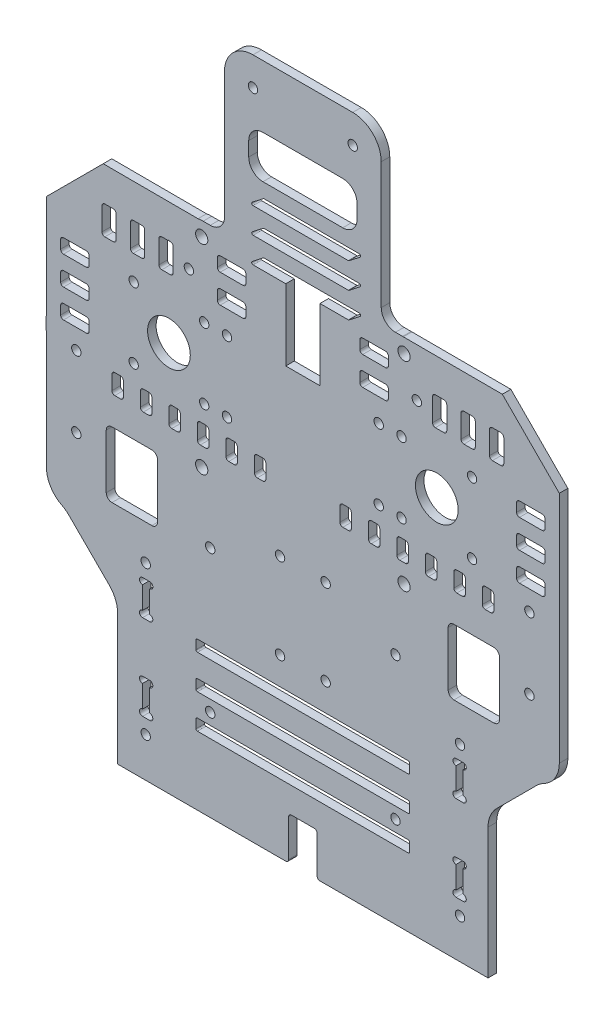
SolidWorks part; units mm, degrees
material "Thornel Mat VMA"
ref_plane "前视基准面" through (0, 0, 0) normal (0, 0, 1) x (1, 0, 0)
ref_plane "上视基准面" through (0, 0, 0) normal (0, 1, 0) x (1, 0, 0)
ref_plane "右视基准面" through (0, 0, 0) normal (1, 0, 0) x (0, 0, -1)
sketch "草图1" plane through (0, 0, 0) normal (0, 0, 1) x (1, 0, 0)
  line L1 (105, -75) -> (-105, -75)
  line L2 (105, -75) -> (105, 75)
  line L3 (105, 75) -> (-105, 75)
  line L4 (-105, -75) -> (-105, 75)
  line L5 (105, -75) -> (-105, 75) construction
  line L6 (105, 75) -> (-105, -75) construction
  line L7 (35.5, -25) -> (-35.5, -25) construction
  line L8 (35.5, -25) -> (35.5, 45) construction
  line L9 (35.5, 45) -> (-35.5, 45) construction
  line L10 (-35.5, -25) -> (-35.5, 45) construction
  line L11 (35.5, -25) -> (-35.5, 45) construction
  line L12 (35.5, 45) -> (-35.5, -25) construction
  circle A0 centre (-35.5, 45) radius 2.15
  circle A1 centre (35.5, 45) radius 2.15
  circle A2 centre (-35.5, -25) radius 2.15
  circle A3 centre (35.5, -25) radius 2.15
  point P0 (0, 0)
  point P5 (0, 10)
  dimension "D6" = 4.3
  dimension "D7" = 4.3
  dimension "D8" = 4.3
  dimension "D9" = 4.3
  dimension "D1" = 150
  dimension "D2" = 210
  dimension "D3" = 70
  dimension "D4" = 71
  dimension "D5" = 10
extrude "凸台-拉伸1" add sketch "草图1" along normal blind 3
sketch "草图2" plane through (0, 0, 3) normal (0, 0, 1) x (1, 0, 0)
  line L0 (0, 0) -> (0, -58.5464) construction
  circle A0 centre (-8, -38.3) radius 1.65
  circle A1 centre (-8, -68.3) radius 1.65
  circle A2 centre (-35.5, -25) radius 2.15 construction
  circle A3 centre (8, -68.3) radius 1.65
  circle A4 centre (8, -38.3) radius 1.65
  dimension "D1" = 3.3
  dimension "D2" = 3.3
  dimension "D4" = 27.5
  dimension "D5" = 13.3
  dimension "D3" = 30
extrude "切除-拉伸1" cut sketch "草图2" against normal blind 10
sketch "草图3" plane through (0, 0, 0) normal (0, 0, -1) x (-1, 0, 0)
  line L0 (34.6256, -5.3744) -> (34.6256, 19.3744) construction
  line L1 (-28.75, 7) -> (98.7077, 7) construction
  line L2 (0, 0) -> (0, 47.7438) construction
  line L3 (-34.6256, -5.3744) -> (-59.3744, -5.3744) construction
  line L7 (-34.6256, -5.3744) -> (-34.6256, 19.3744) construction
  line L8 (-34.6256, 19.3744) -> (-59.3744, 19.3744) construction
  line L9 (-59.3744, -5.3744) -> (-59.3744, 19.3744) construction
  line L10 (-34.6256, -5.3744) -> (-59.3744, 19.3744) construction
  line L11 (-34.6256, 19.3744) -> (-59.3744, -5.3744) construction
  line L12 (59.3744, -5.3744) -> (59.3744, 19.3744) construction
  circle A0 centre (-47, 7) radius 7.5
  circle A1 centre (47, 7) radius 7.5
  circle A2 centre (-59.3744, 19.3744) radius 1.65
  circle A9 centre (-34.6256, 19.3744) radius 1.65
  circle A10 centre (-59.3744, -5.3744) radius 1.65
  circle A11 centre (-34.6256, -5.3744) radius 1.65
  circle A12 centre (34.6256, -5.3744) radius 1.65
  circle A13 centre (34.6256, 19.3744) radius 1.65
  circle A14 centre (59.3744, -5.3744) radius 1.65
  circle A15 centre (59.3744, 19.3744) radius 1.65
  dimension "D1" = 15
  dimension "D2" = 94
  dimension "D3" = 17.5
  dimension "D4" = 3.3
  dimension "D7" = 7
extrude "切除-拉伸2" cut sketch "草图3" against normal blind 10
sketch "草图4" plane through (0, 75, 0) normal (0, 1, 0) x (1, 0, 0)
  line L0 (105, 0) -> (-105, 0) construction
  line L1 (27.5, -3) -> (-27.5, -3)
  line L2 (27.5, -3) -> (27.5, 0)
  line L3 (27.5, 0) -> (-27.5, 0)
  line L4 (-27.5, -3) -> (-27.5, 0)
  line L5 (27.5, -3) -> (-27.5, 0) construction
  line L6 (27.5, 0) -> (-27.5, -3) construction
  point P0 (0, -1.5)
  dimension "D1" = 3
  dimension "D2" = 55
extrude "凸台-拉伸2" add sketch "草图4" along normal blind 34.32
fillet "圆角1" radius 10 2 edges at (27.5, 109.32, 1.5) (-27.5, 109.32, 1.5)
sketch "草图5" plane through (0, 0, 3) normal (0, 0, 1) x (1, 0, 0)
  circle A0 centre (-17.5, 99.32) radius 1.65
  circle A1 centre (17.5, 99.32) radius 1.65
  dimension "D1" = 3.3
  dimension "D2" = 3.3
extrude "切除-拉伸3" cut sketch "草图5" against normal blind 50
sketch "草图6" plane through (0, -75, 0) normal (0, -1, 0) x (1, 0, 0)
  line L4 (-105, 0) -> (105, 0)
  line L5 (105, 0) -> (105, 3)
  line L6 (105, 3) -> (-105, 3)
  line L7 (-105, 3) -> (-105, 0)
  line L8 (-105, 0) -> (105, 0)
  line L9 (105, 0) -> (105, 3)
  line L10 (105, 3) -> (-105, 3)
  line L11 (-105, 3) -> (-105, 0)
  dimension "D1" = 0
extrude "凸台-拉伸3" add sketch "草图6" along normal blind 50
sketch "草图7" plane through (0, 0, 3) normal (0, 0, 1) x (1, 0, 0)
  line L1 (-27.5, 75) -> (-105, 75)
  line L2 (-27.5, 75) -> (-27.5, 50)
  line L3 (-27.5, 50) -> (-105, 50)
  line L4 (-105, 75) -> (-105, 50)
  line L5 (-105, 75) -> (-105, -125) construction
  line L7 (27.5, 75) -> (105, 75)
  line L8 (27.5, 75) -> (27.5, 50)
  line L9 (27.5, 50) -> (105, 50)
  line L10 (105, 75) -> (105, 50)
  line L11 (105, -125) -> (105, 75) construction
  dimension "D1" = 25
  dimension "D2" = 77.5
  dimension "D3" = 25
  dimension "D4" = 77.5
extrude "切除-拉伸4" cut sketch "草图7" against normal blind 50
fillet "圆角2" radius 5 2 edges at (27.5, 50, 1.5) (-27.5, 50, 1.5)
chamfer "倒角1" distance 40 distance2 20 2 edges at (105, 50, 1.5) (-105, 50, 1.5) first distance on face at (68.75, 50, 1.5) first distance on face at (-68.75, 50, 1.5)
sketch "草图10" plane through (0, 0, 3) normal (0, 0, 1) x (1, 0, 0)
  line L0 (105, -125) -> (-105, -125) construction
  line L1 (19, -13.5) -> (-19, -13.5)
  line L2 (19, -13.5) -> (19, 28.5)
  line L3 (19, 28.5) -> (10, 28.5)
  line L4 (-19, -13.5) -> (-19, 28.5)
  line L5 (19, -13.5) -> (-19, 28.5) construction
  line L6 (19, 28.5) -> (0, 7.5) construction
  line L7 (-10, 28.5) -> (-10, 60)
  line L9 (10, 28.5) -> (10, 60)
  line L10 (10, 60) -> (-10, 60)
  line L12 (10, 0) -> (-10, 60) construction
  line L13 (10, 60) -> (-10, 0) construction
  line L14 (-10, 28.5) -> (-19, 28.5)
  point P0 (0, 7.5)
  point P12 (0, 30)
  dimension "D1" = 42
  dimension "D2" = 38
  dimension "D3" = 111.5
  dimension "D4" = 60
  dimension "D5" = 20
extrude "切除-拉伸7" cut sketch "草图10" against normal blind 13
fillet "圆角3" radius 2 8 edges at (19, -13.5, 1.5) (-19, -13.5, 1.5) (-19, 28.5, 1.5) (-10, 28.5, 1.5) (10, 28.5, 1.5) (19, 28.5, 1.5) (10, 60, 1.5) (-10, 60, 1.5)
sketch "草图11" plane through (0, 0, 3) normal (0, 0, 1) x (1, 0, 0)
  line L0 (0, 0) -> (0, 66.5643) construction
  circle A0 centre (-14.35, 31.62) radius 2.1
  circle A1 centre (-47, 7) radius 7.5 construction
  circle A2 centre (14.35, 31.62) radius 2.1
  dimension "D1" = 4.2
  dimension "D2" = 28.7
  dimension "D3" = 24.62
extrude "切除-拉伸8" cut sketch "草图11" against normal blind 10
sketch "草图12" plane through (0, 0, 3) normal (0, 0, 1) x (1, 0, 0)
  line L0 (-14.35, 31.62) -> (14.35, 31.62) construction
  line L1 (0, 31.62) -> (0, -16.21) construction
  circle A0 centre (0, -16.21) radius 2.2
  dimension "D1" = 4.4
  dimension "D2" = 47.83
extrude "切除-拉伸9" cut sketch "草图12" against normal blind 10
sketch "草图19" plane through (0, -125, 0) normal (0, -1, 0) x (1, 0, 0)
  line L4 (-105, 3) -> (-105, 0)
  line L5 (-105, 0) -> (105, 0)
  line L6 (-105, 3) -> (-105, 0)
  line L7 (105, 3) -> (-105, 3)
  line L9 (-105, 0) -> (105, 0)
  line L11 (105, 3) -> (-105, 3)
  line L12 (105, 0) -> (105, 3)
  line L13 (105, 0) -> (105, 3)
  dimension "D1" = 0
extrude "凸台-拉伸4" add sketch "草图19" along normal blind 10
sketch "草图14" plane through (0, 0, 3) normal (0, 0, 1) x (1, 0, 0)
  line L0 (-105, 30) -> (-105, -135) construction
  line L1 (-105, -140.9011) -> (-90, -140.9011)
  line L2 (-105, -140.9011) -> (-105, 59.0989)
  line L3 (-105, 59.0989) -> (-90, 59.0989)
  line L4 (-90, -140.9011) -> (-90, 59.0989)
  line L5 (90, -129.2813) -> (105, -129.2813)
  line L6 (90, -129.2813) -> (90, 70.7187)
  line L7 (90, 70.7187) -> (105, 70.7187)
  line L8 (105, -129.2813) -> (105, 70.7187)
  line L9 (105, -135) -> (105, 30) construction
  dimension "D1" = 200
  dimension "D2" = 15
extrude "切除-拉伸11" cut sketch "草图14" against normal blind 10
sketch "草图17" plane through (0, 0, 3) normal (0, 0, 1) x (1, 0, 0)
  circle A2 centre (-40, 33) radius 1.65
  circle A3 centre (40, 33) radius 1.65
  dimension "D1" = 80
  dimension "D2" = 40
  dimension "D3" = 33
  dimension "D4" = 3.3
  dimension "D5" = 3.3
extrude "切除-拉伸14" cut sketch "草图17" against normal blind 10
sketch "草图20" plane through (0, 0, 3) normal (0, 0, 1) x (1, 0, 0)
  line L1 (90, -129.2813) -> (116.0619, -129.2813)
  line L2 (90, -129.2813) -> (90, -144.7625)
  line L3 (90, -144.7625) -> (116.0619, -144.7625)
  line L4 (116.0619, -129.2813) -> (116.0619, -144.7625)
extrude "切除-拉伸16" cut sketch "草图20" against normal blind 10
fillet "圆角6" radius 5 6 edges at (90, 37.5, 1.5) (65, 50, 1.5) (-65, 50, 1.5) (-90, 37.5, 1.5) (90, -135, 1.5) (-90, -135, 1.5)
sketch "草图21" plane through (0, 0, 3) normal (0, 0, 1) x (1, 0, 0)
  line L0 (-47, 38) -> (-47, 50)
  line L1 (-63.8197, 50) -> (-32.5, 50) construction
  line L2 (-47, 50) -> (-106.4836, 50)
  line L3 (-106.4836, 50) -> (-107.7614, 0)
  line L4 (-107.7614, 0) -> (-77.1993, 0)
  line L5 (78, 7) -> (106.4751, 7)
  line L6 (106.4751, 7) -> (106.4751, 75.5735)
  line L7 (106.4751, 75.5735) -> (47, 75.5735)
  line L8 (47, 75.5735) -> (47, 38)
  arc A0 (-47, 38) -> (-77.1993, 0) centre (-47, 7) ccw
  arc A1 (78, 7) -> (47, 38) centre (47, 7) ccw
  dimension "D1" = 62
  dimension "D2" = 62
extrude "切除-拉伸19" cut sketch "草图21" against normal blind 10
fillet "圆角7" radius 12 4 edges at (90, 7, 1.5) (47, 50, 1.5) (-90, 0, 1.5) (-47, 50, 1.5)
fillet "圆角8" radius 12 2 edges at (78, 7, 1.5) (47, 38, 1.5)
sketch "草图22" plane through (0, 0, 3) normal (0, 0, 1) x (1, 0, 0)
  line L4 (0, 0) -> (0, 90.8471) construction
  line L5 (-90, -12) -> (-70.9724, 1.1695)
  line L6 (-70.9724, 1.1695) -> (-64.1055, 22.5626)
  line L7 (-64.1055, 22.5626) -> (-46.1458, 39.0697)
  line L8 (-46.1458, 39.0697) -> (-35, 50)
  arc A2 (-35, 50) -> (-90, -12) centre (-31.5, -8.5) ccw
  arc A22 (45.6725, 43.4861) -> (35, 50) centre (35, 38) ccw construction
  arc A23 (45.6725, 43.4861) -> (53.7371, 37.2591) centre (56.345, 48.9723) ccw construction
  arc A24 (77.2591, 13.7371) -> (53.7371, 37.2591) centre (47, 7) ccw construction
  arc A25 (77.2591, 13.7371) -> (83.4861, 5.6725) centre (88.9723, 16.345) ccw construction
  arc A26 (90, -5) -> (83.4861, 5.6725) centre (78, -5) ccw construction
  arc A31 (45.6725, 43.4861) -> (35, 50) centre (35, 38) ccw
  arc A32 (45.6725, 43.4861) -> (53.7371, 37.2591) centre (56.345, 48.9723) ccw
  arc A33 (77.2591, 13.7371) -> (53.7371, 37.2591) centre (47, 7) ccw
  arc A34 (77.2591, 13.7371) -> (83.4861, 5.6725) centre (88.9723, 16.345) ccw
  arc A35 (90, -5) -> (83.4861, 5.6725) centre (78, -5) ccw
  arc A36 (35, 50) -> (90, -5) centre (35, -5) cw
extrude "凸台-拉伸5" add sketch "草图22" against normal up to surface (3 mm away) up to face at (-38.35, 33, 0)
sketch "草图24" plane through (0, 0, 3) normal (0, 0, 1) x (1, 0, 0)
  line L1 (-90, -135) -> (-45, -135)
  line L2 (-90, -135) -> (-90, -50)
  line L3 (-90, -50) -> (-45, -50)
  line L4 (-45, -135) -> (-45, -50)
  line L5 (90, -135) -> (45, -135)
  line L6 (90, -135) -> (90, -50)
  line L7 (90, -50) -> (45, -50)
  line L8 (45, -135) -> (45, -50)
  line L9 (85, -135) -> (-85, -135) construction
  dimension "D1" = 85
  dimension "D2" = 45
  dimension "D3" = 85
  dimension "D4" = 45
extrude "切除-拉伸20" cut sketch "草图24" against normal blind 10
sketch "草图25" plane through (0, 0, 3) normal (0, 0, 1) x (1, 0, 0)
  line L1 (-45, -135) -> (45, -135)
  line L2 (-45, -135) -> (-45, -130)
  line L3 (-45, -130) -> (45, -130)
  line L4 (45, -135) -> (45, -130)
  line L5 (45, -50) -> (45, -135) construction
  dimension "D1" = 5
  dimension "D2" = 90
extrude "切除-拉伸21" cut sketch "草图25" against normal blind 30
sketch "草图26" plane through (0, 0, 3) normal (0, 0, 1) x (1, 0, 0)
  line L1 (32.5, -98) -> (-32.5, -98) construction
  line L2 (32.5, -98) -> (32.5, -48) construction
  line L3 (32.5, -48) -> (-32.5, -48) construction
  line L4 (-32.5, -98) -> (-32.5, -48) construction
  line L5 (32.5, -98) -> (-32.5, -48) construction
  line L6 (32.5, -48) -> (-32.5, -98) construction
  circle A0 centre (-32.5, -48) radius 1.65
  circle A1 centre (32.5, -48) radius 1.65
  circle A2 centre (-32.5, -98) radius 1.65
  circle A3 centre (32.5, -98) radius 1.65
  point P0 (0, -73)
  dimension "D1" = 3.3
  dimension "D2" = 3.3
  dimension "D3" = 3.3
  dimension "D4" = 3.3
  dimension "D5" = 65
  dimension "D6" = 73
  dimension "D7" = 50
extrude "切除-拉伸22" cut sketch "草图26" against normal blind 10
sketch "草图27" plane through (0, 0, 3) normal (0, 0, 1) x (1, 0, 0)
  line L0 (-45, -130) -> (-45, -50) construction
  line L1 (0, 0) -> (0, -119.9082) construction
  circle A0 centre (-40, -93) radius 1.65
  circle A1 centre (-35.5, -25) radius 2.15 construction
  circle A2 centre (40, -93) radius 1.65
  circle A3 centre (-40, -125) radius 1.65
  circle A4 centre (40, -125) radius 1.65
  dimension "D1" = 3.3
  dimension "D2" = 5
  dimension "D3" = 68
  dimension "D4" = 3.3
  dimension "D5" = 3.3
  dimension "D6" = 32
extrude "切除-拉伸23" cut sketch "草图27" against normal blind 10
sketch "草图28" plane through (0, 0, 3) normal (0, 0, 1) x (1, 0, 0)
  line L10 (-90, -12) -> (-90, 50)
  line L11 (-90, 50) -> (-36.7963, 49.8648)
  line L12 (90, -5) -> (90, 49.8648)
  line L13 (90, 49.8648) -> (35, 50)
  arc A8 (-36.7963, 49.8648) -> (-90, -12) centre (13.2997, -47.0278) ccw
  arc A9 (90, -5) -> (35, 50) centre (5.4098, -34.5902) ccw
extrude "凸台-拉伸6" add sketch "草图28" against normal up to surface (3 mm away) up to face at (41.65, -93, 0)
sketch "草图29" plane through (0, 0, 3) normal (0, 0, 1) x (1, 0, 0)
  line L1 (19, 72.5) -> (-19, 72.5)
  line L2 (19, 72.5) -> (19, 87.5)
  line L3 (19, 87.5) -> (-19, 87.5)
  line L4 (-19, 72.5) -> (-19, 87.5)
  line L5 (19, 72.5) -> (-19, 87.5) construction
  line L6 (19, 87.5) -> (-19, 72.5) construction
  point P0 (0, 80)
  dimension "D1" = 80
  dimension "D2" = 38
  dimension "D3" = 15
extrude "切除-拉伸24" cut sketch "草图29" against normal blind 5
fillet "圆角10" radius 5 4 edges at (19, 72.5, 1.5) (-19, 72.5, 1.5) (19, 87.5, 1.5) (-19, 87.5, 1.5)
sketch "草图31" plane through (0, 0, 3) normal (0, 0, 1) x (1, 0, 0)
  line L0 (-45, -114) -> (45, -114) construction
  line L1 (45, -50) -> (45, -130) construction
  line L2 (-45, -130) -> (-45, -50) construction
  line L3 (45, -130) -> (-45, -130) construction
  text T0 "<b>WH</b>" font "Mistral" height 17
  dimension "D1" = 16
sketch "草图32" plane through (0, 0, 3) normal (0, 0, 1) x (1, 0, 0)
  line L0 (-40, -93) -> (40, -93) construction
  text T0 "HIT" font "Mistral" height 17
sketch "草图35" plane through (0, 0, 3) normal (0, 0, 1) x (1, 0, 0)
  circle A0 centre (-40, -93) radius 1.8443
  circle A1 centre (-40, -125) radius 3.6058
  circle A2 centre (40, -125) radius 3.1105
  circle A3 centre (40, -93) radius 3.0337
extrude "凸台-拉伸7" add sketch "草图35" against normal up to surface (3 mm away) up to face at (0, 80, 0)
sketch "草图36" plane through (0, 0, 3) normal (0, 0, 1) x (1, 0, 0)
  line L1 (-45, -50) -> (-65, -50)
  line L2 (-45, -50) -> (-45, -130)
  line L3 (-45, -130) -> (-65, -130)
  line L4 (-65, -50) -> (-65, -130)
  line L5 (45, -50) -> (65, -50)
  line L6 (45, -50) -> (45, -130)
  line L7 (45, -130) -> (65, -130)
  line L8 (65, -50) -> (65, -130)
  dimension "D1" = 80
  dimension "D2" = 20
  dimension "D3" = 80
  dimension "D4" = 20
extrude "凸台-拉伸8" add sketch "草图36" against normal up to surface (3 mm away) up to face at (0, 80, 0)
sketch "草图37" plane through (0, 0, 0) normal (0, 0, -1) x (-1, 0, 0)
  line L0 (65, -90) -> (-65, -90) construction
  line L1 (53.75, -81.1) -> (56.25, -81.1)
  line L2 (53.75, -78.9) -> (53.75, -71.1)
  line L3 (53.75, -68.9) -> (56.25, -68.9)
  line L4 (56.25, -78.9) -> (56.25, -71.1)
  line L5 (53.75, -81.1) -> (56.25, -68.9) construction
  line L6 (53.75, -68.9) -> (56.25, -81.1) construction
  line L7 (65, -50) -> (65, -130) construction
  line L8 (-65, -130) -> (-65, -50) construction
  line L9 (53.75, -111.1) -> (56.25, -111.1)
  line L10 (56.25, -101.1) -> (56.25, -108.9)
  line L11 (53.75, -98.9) -> (56.25, -98.9)
  line L12 (53.75, -101.1) -> (53.75, -108.9)
  line L13 (0, 0) -> (0, -157.7378) construction
  line L14 (-53.75, -98.9) -> (-56.25, -98.9)
  line L15 (-53.75, -101.1) -> (-53.75, -108.9)
  line L16 (-53.75, -111.1) -> (-56.25, -111.1)
  line L17 (-56.25, -101.1) -> (-56.25, -108.9)
  line L18 (-53.75, -81.1) -> (-56.25, -81.1)
  line L19 (-53.75, -78.9) -> (-53.75, -71.1)
  line L20 (-53.75, -68.9) -> (-56.25, -68.9)
  line L21 (-56.25, -78.9) -> (-56.25, -71.1)
  arc A0 (56.25, -71.1) -> (56.25, -68.9) centre (56.25, -70) ccw
  arc A1 (53.75, -68.9) -> (53.75, -71.1) centre (53.75, -70) ccw
  arc A2 (56.25, -81.1) -> (56.25, -78.9) centre (56.25, -80) ccw
  arc A3 (53.75, -78.9) -> (53.75, -81.1) centre (53.75, -80) ccw
  arc A4 (56.25, -101.1) -> (56.25, -98.9) centre (56.25, -100) ccw
  arc A5 (53.75, -98.9) -> (53.75, -101.1) centre (53.75, -100) ccw
  arc A6 (56.25, -111.1) -> (56.25, -108.9) centre (56.25, -110) ccw
  arc A7 (53.75, -108.9) -> (53.75, -111.1) centre (53.75, -110) ccw
  arc A8 (-56.25, -101.1) -> (-56.25, -98.9) centre (-56.25, -100) cw
  arc A9 (-53.75, -98.9) -> (-53.75, -101.1) centre (-53.75, -100) cw
  arc A10 (-53.75, -108.9) -> (-53.75, -111.1) centre (-53.75, -110) cw
  arc A11 (-56.25, -111.1) -> (-56.25, -108.9) centre (-56.25, -110) cw
  arc A12 (-56.25, -81.1) -> (-56.25, -78.9) centre (-56.25, -80) cw
  arc A13 (-53.75, -78.9) -> (-53.75, -81.1) centre (-53.75, -80) cw
  arc A14 (-53.75, -68.9) -> (-53.75, -71.1) centre (-53.75, -70) cw
  arc A15 (-56.25, -71.1) -> (-56.25, -68.9) centre (-56.25, -70) cw
  point P0 (55, -75)
  dimension "D5" = 2.2
  dimension "D6" = 2.2
  dimension "D7" = 2.2
  dimension "D8" = 2.2
  dimension "D9" = 2.2
  dimension "D10" = 2.2
  dimension "D11" = 2.2
  dimension "D12" = 2.2
  dimension "D1" = 12.2
  dimension "D2" = 2.5
  dimension "D3" = 55
  dimension "D4" = 75
extrude "切除-拉伸30" cut sketch "草图37" against normal through all
sketch "草图38" plane through (0, 0, 3) normal (0, 0, 1) x (1, 0, 0)
  line L0 (-56.25, -78.9) -> (-56.25, -71.1) construction
  line L1 (-56.25, -68.9) -> (-53.75, -68.9) construction
  line L2 (-56.25, -108.9) -> (-56.25, -101.1) construction
  line L3 (-53.75, -111.1) -> (-56.25, -111.1) construction
  line L4 (0, 0) -> (0, -138.952) construction
  circle A0 centre (-55.15, -63.9) radius 1.65
  circle A1 centre (-55.15, -116.1) radius 1.65
  circle A2 centre (55.15, -116.1) radius 1.65
  circle A3 centre (55.15, -63.9) radius 1.65
  dimension "D1" = 3.3
  dimension "D2" = 1.1
  dimension "D4" = 3.3
  dimension "D6" = 5
  dimension "D3" = 5
  dimension "D5" = 1.1
extrude "切除-拉伸31" cut sketch "草图38" against normal blind 12
sketch "草图39" plane through (0, 0, 3) normal (0, 0, 1) x (1, 0, 0)
  line L0 (8, 60) -> (-8, 60) construction
  line L1 (19, -24.4313) -> (-19, -24.4313)
  line L2 (19, -24.4313) -> (19, 60)
  line L3 (19, 60) -> (-19, 60)
  line L4 (-19, -24.4313) -> (-19, 60)
  line L5 (19, -24.4313) -> (-19, 60) construction
  line L6 (19, 60) -> (-19, -24.4313) construction
  line L7 (19, -11.5) -> (19, 26.5) construction
  line L8 (-19, 26.5) -> (-19, -11.5) construction
  point P0 (0, 17.7844)
extrude "凸台-拉伸9" add sketch "草图39" against normal up to surface (3 mm away) up to face at (56.8, -63.9, 0)
sketch "草图40" plane through (0, 0, 3) normal (0, 0, 1) x (1, 0, 0)
  line L0 (-13.7722, 67.5) -> (-18.9064, 63.5)
  line L1 (-13.7722, 67.5) -> (21.2278, 67.5)
  line L2 (-18.9064, 63.5) -> (16.0936, 63.5)
  line L3 (21.2278, 67.5) -> (16.0936, 63.5)
  line L4 (-13.7722, 58.5) -> (-18.9064, 54.5)
  line L5 (-13.7722, 58.5) -> (21.2278, 58.5)
  line L6 (-18.9064, 54.5) -> (16.0936, 54.5)
  line L7 (21.2278, 58.5) -> (16.0936, 54.5)
  line L8 (-13.7722, 49.5) -> (-18.9064, 45.5)
  line L9 (-13.7722, 49.5) -> (21.2278, 49.5)
  line L10 (-18.9064, 45.5) -> (16.0936, 45.5)
  line L11 (21.2278, 49.5) -> (16.0936, 45.5)
  line L12 (-14, 72.5) -> (14, 72.5) construction
  dimension "D1" = 5
  dimension "D2" = 5
  dimension "D3" = 5
  dimension "D4" = 4
  dimension "D5" = 35
  dimension "D6" = 4
  dimension "D7" = 4
  dimension "D8" = 35
  dimension "D9" = 35
extrude "切除-拉伸32" cut sketch "草图40" against normal blind 10
fillet "圆角13" radius 0.5 12 edges at (21.2278, 49.5, 1.5) (21.2278, 58.5, 1.5) (-13.7722, 49.5, 1.5) (-13.7722, 58.5, 1.5) (-18.9064, 45.5, 1.5) (-18.9064, 54.5, 1.5) (16.0936, 45.5, 1.5) (16.0936, 54.5, 1.5) (16.0936, 63.5, 1.5) (21.2278, 67.5, 1.5) (-18.9064, 63.5, 1.5) (-13.7722, 67.5, 1.5)
sketch "草图42" plane through (0, 0, 3) normal (0, 0, 1) x (1, 0, 0)
  line L0 (0, 0) -> (0, 28.5736) construction
  circle A1 centre (-26.6256, 19.3744) radius 1.65
  circle A2 centre (-26.6256, -5.3744) radius 1.65
  circle A3 centre (-34.6256, 19.3744) radius 1.65 construction
  circle A4 centre (-34.6256, -5.3744) radius 1.65 construction
  circle A5 centre (26.6256, -5.3744) radius 1.65
  circle A6 centre (26.6256, 19.3744) radius 1.65
  dimension "D1" = 3.3
  dimension "D2" = 3.3
  dimension "D3" = 8
  dimension "D4" = 8
extrude "切除-拉伸34" cut sketch "草图42" against normal blind 3
sketch "草图43" plane through (0, 0, 3) normal (0, 0, 1) x (1, 0, 0)
  line L0 (65, -130) -> (-65, -130) construction
  line L1 (5, -145) -> (-5, -145)
  line L2 (5, -145) -> (5, -115)
  line L3 (5, -115) -> (-5, -115)
  line L4 (-5, -145) -> (-5, -115)
  line L5 (5, -145) -> (-5, -115) construction
  line L6 (5, -115) -> (-5, -145) construction
  point P0 (0, -130)
  dimension "D1" = 30
  dimension "D2" = 10
extrude "切除-拉伸35" cut sketch "草图43" against normal blind 10
fillet "圆角15" radius 1 4 edges at (-5, -130, 1.5) (5, -130, 1.5) (5, -115, 1.5) (-5, -115, 1.5)
sketch "草图44" plane through (0, -50, 0) normal (0, -1, 0) x (1, 0, 0)
  line L4 (-90, 0) -> (-65, 0)
  line L5 (-65, 0) -> (-65, 3)
  line L6 (-65, 3) -> (-90, 3)
  line L7 (-90, 3) -> (-90, 0)
  line L8 (-90, 0) -> (-65, 0)
  line L9 (-65, 0) -> (-65, 3)
  line L10 (-65, 3) -> (-90, 3)
  line L11 (-90, 3) -> (-90, 0)
  line L12 (90, 3) -> (65, 3)
  line L13 (65, 3) -> (65, 0)
  line L14 (65, 0) -> (90, 0)
  line L15 (90, 0) -> (90, 3)
  line L16 (90, 3) -> (65, 3)
  line L17 (65, 3) -> (65, 0)
  line L18 (65, 0) -> (90, 0)
  line L19 (90, 0) -> (90, 3)
  dimension "D1" = 0
  dimension "D2" = 0
extrude "凸台-拉伸10" add sketch "草图44" along normal blind 10
sketch "草图9" plane through (0, 0, 3) normal (0, 0, 1) x (1, 0, 0)
  line L0 (-69.75, -24) -> (-105, -24) construction
  line L2 (-79.5, -36.5) -> (-79.5, -11.5) construction
  line L3 (0, 0) -> (0, 51.3549) construction
  line L4 (79.5, -36.5) -> (79.5, -11.5) construction
  line L5 (-35, 50) -> (-32.5, 50) construction
  arc A0 (-90, -5) -> (-90, -12) centre (-31.5, -8.5) ccw construction
  circle A1 centre (-79.5, -11.5) radius 1.65
  circle A2 centre (-79.5, -36.5) radius 1.65
  circle A3 centre (79.5, -36.5) radius 1.65
  circle A4 centre (79.5, -11.5) radius 1.65
  point P9 (-79.5, -24)
  point P18 (79.5, -24)
  point P20 (-90.1046, -8.5)
  dimension "D3" = 3.3
  dimension "D4" = 3.3
  dimension "D2" = 10.6046
  dimension "D1" = 25
  dimension "D5" = 74
extrude "切除-拉伸6" cut sketch "草图9" against normal blind 10
chamfer "倒角3" distance 20 angle 45 2 edges at (65, -60, 1.5) (-65, -60, 1.5)
fillet "圆角16" radius 10 4 edges at (-65, -80, 1.5) (-85, -60, 1.5) (65, -80, 1.5) (85, -60, 1.5)
sketch "草图45" plane through (0, 0, 3) normal (0, 0, 1) x (1, 0, 0)
  line L0 (65, -130) -> (6, -130) construction
  line L1 (37.5, -78) -> (-37.5, -78)
  line L2 (37.5, -78) -> (37.5, -82)
  line L3 (37.5, -82) -> (-37.5, -82)
  line L4 (-37.5, -78) -> (-37.5, -82)
  line L5 (37.5, -78) -> (-37.5, -82) construction
  line L6 (37.5, -82) -> (-37.5, -78) construction
  line L7 (37.5, -90) -> (37.5, -94)
  line L8 (37.5, -90) -> (-37.5, -90)
  line L9 (-37.5, -90) -> (-37.5, -94)
  line L10 (37.5, -94) -> (-37.5, -94)
  line L11 (37.5, -102) -> (37.5, -106)
  line L12 (37.5, -102) -> (-37.5, -102)
  line L13 (-37.5, -102) -> (-37.5, -106)
  line L14 (37.5, -106) -> (-37.5, -106)
  point P0 (0, -80)
  dimension "D1" = 4
  dimension "D2" = 75
  dimension "D3" = 50
  dimension "D4" = 3
extrude "切除-拉伸36" cut sketch "草图45" against normal blind 10
fillet "圆角18" radius 0.5 12 edges at (37.5, -106, 1.5) (37.5, -94, 1.5) (-37.5, -102, 1.5) (-37.5, -90, 1.5) (-37.5, -94, 1.5) (-37.5, -106, 1.5) (37.5, -102, 1.5) (37.5, -90, 1.5) (37.5, -82, 1.5) (37.5, -78, 1.5) (-37.5, -82, 1.5) (-37.5, -78, 1.5)
fillet "圆角19" radius 10 2 edges at (-90, -60, 1.5) (90, -60, 1.5)
sketch "草图46" plane through (0, 0, 0) normal (0, 0, -1) x (-1, 0, 0)
  line L0 (17.4511, 45.5) -> (-15.9218, 45.5) construction
  line L1 (6, 20.5) -> (-6, 20.5)
  line L2 (6, 20.5) -> (6, 45.5)
  line L3 (6, 45.5) -> (-6, 45.5)
  line L4 (-6, 20.5) -> (-6, 45.5)
  line L5 (6, 20.5) -> (-6, 45.5) construction
  line L6 (6, 45.5) -> (-6, 20.5) construction
  point P0 (0, 33)
  dimension "D1" = 25
  dimension "D2" = 12
extrude "切除-拉伸37" cut sketch "草图46" against normal blind 10
sketch "草图47" plane through (0, 0, 0) normal (0, 0, -1) x (-1, 0, 0)
  line L1 (-20, 37.5) -> (-30, 37.5)
  line L2 (-20, 37.5) -> (-20, 42.5)
  line L3 (-20, 42.5) -> (-30, 42.5)
  line L4 (-30, 37.5) -> (-30, 42.5)
  line L5 (-20, 37.5) -> (-30, 42.5) construction
  line L6 (-20, 42.5) -> (-30, 37.5) construction
  line L7 (-20, 27.5) -> (-30, 27.5)
  line L8 (-20, 27.5) -> (-20, 32.5)
  line L9 (-20, 32.5) -> (-30, 32.5)
  line L10 (-30, 27.5) -> (-30, 32.5)
  line L11 (-20, 27.5) -> (-30, 32.5) construction
  line L12 (-20, 32.5) -> (-30, 27.5) construction
  line L13 (-45.5, 28) -> (-50.5, 28)
  line L14 (-45.5, 28) -> (-45.5, 38)
  line L15 (-45.5, 38) -> (-50.5, 38)
  line L16 (-50.5, 28) -> (-50.5, 38)
  line L17 (-45.5, 28) -> (-50.5, 38) construction
  line L18 (-45.5, 38) -> (-50.5, 28) construction
  line L19 (-55.5, 28) -> (-60.5, 28)
  line L20 (-55.5, 28) -> (-55.5, 38)
  line L21 (-55.5, 38) -> (-60.5, 38)
  line L22 (-60.5, 28) -> (-60.5, 38)
  line L23 (-55.5, 28) -> (-60.5, 38) construction
  line L24 (-55.5, 38) -> (-60.5, 28) construction
  line L25 (-70.5, 28) -> (-65.5, 28)
  line L26 (-70.5, 28) -> (-70.5, 38)
  line L27 (-70.5, 38) -> (-65.5, 38)
  line L28 (-65.5, 28) -> (-65.5, 38)
  line L29 (-70.5, 28) -> (-65.5, 38) construction
  line L30 (-70.5, 38) -> (-65.5, 28) construction
  line L31 (-85, 15.5) -> (-75, 15.5)
  line L32 (-85, 15.5) -> (-85, 20.5)
  line L33 (-85, 20.5) -> (-75, 20.5)
  line L34 (-75, 15.5) -> (-75, 20.5)
  line L35 (-85, 15.5) -> (-75, 20.5) construction
  line L36 (-85, 20.5) -> (-75, 15.5) construction
  line L37 (-75, 5.5) -> (-85, 5.5)
  line L38 (-75, 5.5) -> (-75, 10.5)
  line L39 (-75, 10.5) -> (-85, 10.5)
  line L40 (-85, 5.5) -> (-85, 10.5)
  line L41 (-75, 5.5) -> (-85, 10.5) construction
  line L42 (-75, 10.5) -> (-85, 5.5) construction
  line L43 (-75, -4.5) -> (-85, -4.5)
  line L44 (-75, -4.5) -> (-75, 0.5)
  line L45 (-75, 0.5) -> (-85, 0.5)
  line L46 (-85, -4.5) -> (-85, 0.5)
  line L47 (-75, -4.5) -> (-85, 0.5) construction
  line L48 (-75, 0.5) -> (-85, -4.5) construction
  point P0 (-25, 40)
  point P5 (-25, 30)
  point P10 (-48, 33)
  point P15 (-58, 33)
  point P20 (-68, 33)
  point P25 (-80, 18)
  point P30 (-80, 8)
  point P35 (-80, -2)
  dimension "D1" = 5
  dimension "D2" = 10
  dimension "D3" = 5
  dimension "D4" = 10
  dimension "D5" = 10
  dimension "D6" = 5
  dimension "D7" = 10
  dimension "D8" = 5
  dimension "D9" = 10
  dimension "D10" = 5
  dimension "D11" = 5
  dimension "D12" = 10
  dimension "D13" = 5
  dimension "D14" = 10
  dimension "D15" = 5
  dimension "D16" = 10
  dimension "D17" = 25
  dimension "D18" = 30
  dimension "D19" = 10
  dimension "D20" = 33
  dimension "D21" = 10
  dimension "D22" = 10
  dimension "D23" = 48
  dimension "D24" = 10
  dimension "D25" = 10
  dimension "D26" = 80
  dimension "D27" = 18
extrude "切除-拉伸38" cut sketch "草图47" against normal blind 10
sketch "草图48" plane through (0, 0, 0) normal (0, 0, -1) x (-1, 0, 0)
  line L0 (-23, -17.5) -> (-23, -12.5)
  line L1 (-14, -18.5) -> (-16, -18.5)
  line L2 (-13, -17.5) -> (-13, -12.5)
  line L3 (-14, -11.5) -> (-16, -11.5)
  line L4 (-17, -17.5) -> (-17, -12.5)
  line L5 (-13, -18.5) -> (-17, -11.5) construction
  line L6 (-13, -11.5) -> (-17, -18.5) construction
  line L7 (-24, -18.5) -> (-26, -18.5)
  line L8 (-27, -17.5) -> (-27, -12.5)
  line L9 (-24, -11.5) -> (-26, -11.5)
  line L10 (-33, -17.5) -> (-33, -12.5)
  line L11 (-34, -18.5) -> (-36, -18.5)
  line L12 (-37, -17.5) -> (-37, -12.5)
  line L13 (-34, -11.5) -> (-36, -11.5)
  line L14 (-43, -17.5) -> (-43, -12.5)
  line L15 (-44, -18.5) -> (-46, -18.5)
  line L16 (-47, -17.5) -> (-47, -12.5)
  line L17 (-44, -11.5) -> (-46, -11.5)
  line L18 (-53, -17.5) -> (-53, -12.5)
  line L19 (-54, -18.5) -> (-56, -18.5)
  line L20 (-57, -17.5) -> (-57, -12.5)
  line L21 (-54, -11.5) -> (-56, -11.5)
  line L22 (-63, -17.5) -> (-63, -12.5)
  line L23 (-64, -18.5) -> (-66, -18.5)
  line L24 (-67, -17.5) -> (-67, -12.5)
  line L25 (-64, -11.5) -> (-66, -11.5)
  arc A0 (-14, -18.5) -> (-13, -17.5) centre (-14, -17.5) ccw
  arc A1 (-16, -18.5) -> (-17, -17.5) centre (-16, -17.5) cw
  arc A2 (-13, -12.5) -> (-14, -11.5) centre (-14, -12.5) ccw
  arc A3 (-16, -11.5) -> (-17, -12.5) centre (-16, -12.5) ccw
  arc A4 (-23, -12.5) -> (-24, -11.5) centre (-24, -12.5) ccw
  arc A5 (-24, -18.5) -> (-23, -17.5) centre (-24, -17.5) ccw
  arc A6 (-26, -18.5) -> (-27, -17.5) centre (-26, -17.5) cw
  arc A7 (-26, -11.5) -> (-27, -12.5) centre (-26, -12.5) ccw
  arc A8 (-33, -12.5) -> (-34, -11.5) centre (-34, -12.5) ccw
  arc A9 (-34, -18.5) -> (-33, -17.5) centre (-34, -17.5) ccw
  arc A10 (-36, -18.5) -> (-37, -17.5) centre (-36, -17.5) cw
  arc A11 (-36, -11.5) -> (-37, -12.5) centre (-36, -12.5) ccw
  arc A12 (-43, -12.5) -> (-44, -11.5) centre (-44, -12.5) ccw
  arc A13 (-44, -18.5) -> (-43, -17.5) centre (-44, -17.5) ccw
  arc A14 (-46, -18.5) -> (-47, -17.5) centre (-46, -17.5) cw
  arc A15 (-46, -11.5) -> (-47, -12.5) centre (-46, -12.5) ccw
  arc A16 (-53, -12.5) -> (-54, -11.5) centre (-54, -12.5) ccw
  arc A17 (-54, -18.5) -> (-53, -17.5) centre (-54, -17.5) ccw
  arc A18 (-56, -18.5) -> (-57, -17.5) centre (-56, -17.5) cw
  arc A19 (-56, -11.5) -> (-57, -12.5) centre (-56, -12.5) ccw
  arc A20 (-63, -12.5) -> (-64, -11.5) centre (-64, -12.5) ccw
  arc A21 (-64, -18.5) -> (-63, -17.5) centre (-64, -17.5) ccw
  arc A22 (-66, -18.5) -> (-67, -17.5) centre (-66, -17.5) cw
  arc A23 (-66, -11.5) -> (-67, -12.5) centre (-66, -12.5) ccw
  point P0 (-15, -15)
  dimension "D5" = 1
  dimension "D1" = 7
  dimension "D2" = 4
  dimension "D3" = 15
  dimension "D4" = 15
  dimension "D6" = 6
extrude "切除-拉伸39" cut sketch "草图48" against normal blind 10
fillet "圆角20" radius 1 32 edges at (30, 27.5, 1.5) (30, 37.5, 1.5) (30, 32.5, 1.5) (30, 42.5, 1.5) (20, 27.5, 1.5) (20, 37.5, 1.5) (20, 32.5, 1.5) (20, 42.5, 1.5) (70.5, 28, 1.5) (60.5, 28, 1.5) (50.5, 28, 1.5) (65.5, 28, 1.5) (55.5, 28, 1.5) (45.5, 28, 1.5) (45.5, 38, 1.5) (55.5, 38, 1.5) (65.5, 38, 1.5) (50.5, 38, 1.5) (60.5, 38, 1.5) (70.5, 38, 1.5) (85, -4.5, 1.5) (85, 5.5, 1.5) (85, 15.5, 1.5) (75, 15.5, 1.5) (75, -4.5, 1.5) (75, 5.5, 1.5) (75, 0.5, 1.5) (75, 10.5, 1.5) (75, 20.5, 1.5) (85, 0.5, 1.5) (85, 10.5, 1.5) (85, 20.5, 1.5)
mirror "镜向1" about plane through (0, 0, 0) normal (1, 0, 0) of "切除-拉伸39", "圆角20", "切除-拉伸38"
sketch "草图49" plane through (0, 0, 0) normal (0, 0, -1) x (-1, 0, 0)
  line L1 (-53, -51.5) -> (-67, -51.5)
  line L2 (-51, -49.5) -> (-51, -30.5)
  line L3 (-53, -28.5) -> (-67, -28.5)
  line L4 (-69, -49.5) -> (-69, -30.5)
  line L5 (-51, -51.5) -> (-69, -28.5) construction
  line L6 (-51, -28.5) -> (-69, -51.5) construction
  line L7 (67, -51.5) -> (53, -51.5)
  line L8 (69, -49.5) -> (69, -30.5)
  line L9 (67, -28.5) -> (53, -28.5)
  line L10 (51, -49.5) -> (51, -30.5)
  line L11 (69, -51.5) -> (51, -28.5) construction
  line L12 (69, -28.5) -> (51, -51.5) construction
  arc A0 (53, -51.5) -> (51, -49.5) centre (53, -49.5) cw
  arc A1 (67, -51.5) -> (69, -49.5) centre (67, -49.5) ccw
  arc A2 (69, -30.5) -> (67, -28.5) centre (67, -30.5) ccw
  arc A3 (53, -28.5) -> (51, -30.5) centre (53, -30.5) ccw
  arc A4 (-67, -51.5) -> (-69, -49.5) centre (-67, -49.5) cw
  arc A5 (-53, -51.5) -> (-51, -49.5) centre (-53, -49.5) ccw
  arc A6 (-51, -30.5) -> (-53, -28.5) centre (-53, -30.5) ccw
  arc A7 (-67, -28.5) -> (-69, -30.5) centre (-67, -30.5) ccw
  point P0 (-60, -40)
  point P5 (60, -40)
  dimension "D8" = 2
  dimension "D1" = 23
  dimension "D2" = 18
  dimension "D3" = 23
  dimension "D4" = 18
  dimension "D5" = 60
  dimension "D6" = 60
  dimension "D7" = 40
extrude "切除-拉伸40" cut sketch "草图49" against normal blind 10
chamfer "倒角4" distance 20 angle 45 2 edges at (-90, 50, 1.5) (90, 49.8648, 1.5) first distance on face at (-90, 22.5, 1.5) first distance on face at (62.6352, 49.9321, 1.125)
